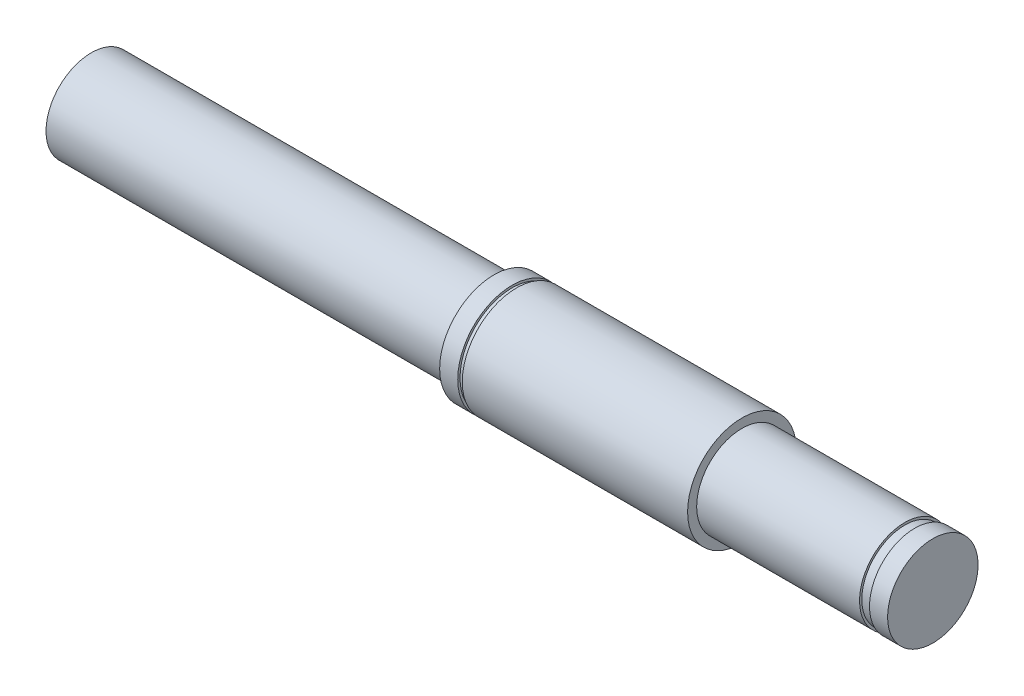
SolidWorks part; units mm, degrees
ref_plane "Front Plane" through (0, 0, 0) normal (0, 0, 1) x (1, 0, 0)
ref_plane "Top Plane" through (0, 0, 0) normal (0, 1, 0) x (1, 0, 0)
ref_plane "Right Plane" through (0, 0, 0) normal (1, 0, 0) x (0, 0, -1)
sketch "Sketch7" plane through (0, 0, 0) normal (0, 0, 1) x (1, 0, 0)
  line L0 (0, 0) -> (1600.6156, 0) construction
  line L1 (-2, 5) -> (-2, 6)
  line L2 (0, 6) -> (-2, 6)
  line L3 (0, 6) -> (0, 5.7496)
  line L4 (-2, 5) -> (-46.5, 5)
  line L5 (-46.5, 5) -> (-46.5, 0)
  line L6 (0, 5.7496) -> (0.5, 5.7496)
  line L7 (0.5, 5.7496) -> (0.5, 6)
  line L8 (0.5, 6) -> (25.4, 6)
  line L9 (25.4, 6) -> (25.4, 5)
  line L10 (25.4, 5) -> (43.4, 5)
  line L11 (43.4, 5) -> (43.4, 4.75)
  line L12 (43.4, 4.75) -> (44.5, 4.75)
  line L13 (44.5, 4.75) -> (44.5, 5)
  line L14 (44.5, 5) -> (46.5, 5)
  line L15 (46.5, 5) -> (46.5, 0)
  line L16 (-46.5, 0) -> (46.5, 0)
  dimension "D1" = 1
  dimension "D2" = 2
  dimension "D3" = 44.5
  dimension "D4" = 5
  dimension "D5" = 0.5
  dimension "D6" = 24.9
  dimension "D7" = 18
  dimension "D8" = 0.25
  dimension "D9" = 0.25
  dimension "D10" = 1.1
  dimension "D11" = 2
revolve "Revolve1" add sketch "Sketch7" angle 360 about L0
scale "Scale1" scale about centroid uniform scaling yes scale factor 0.317565
